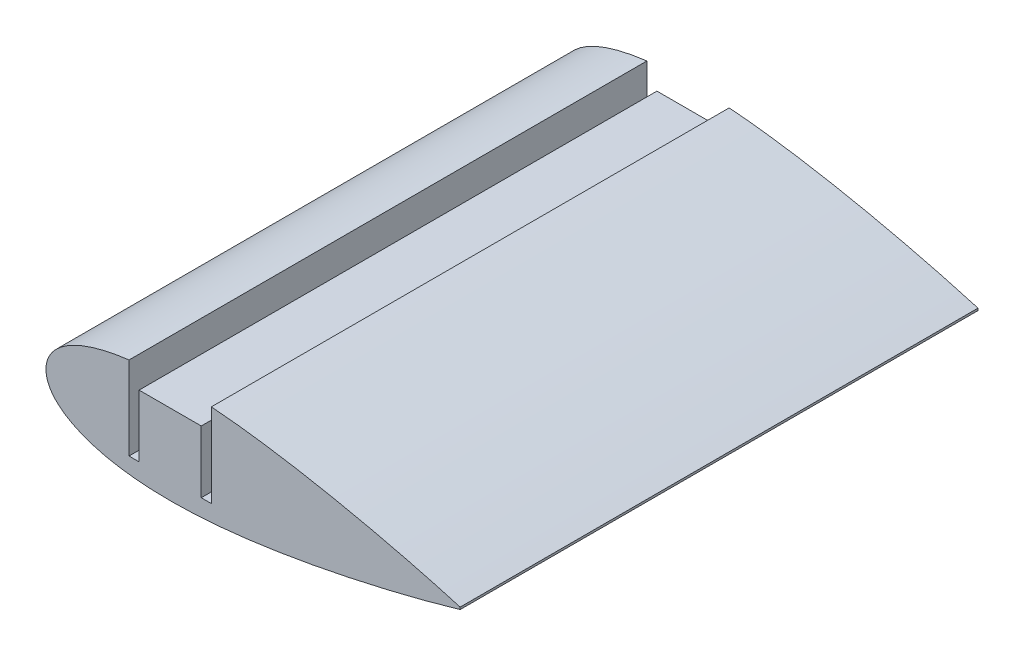
SolidWorks part; units mm, degrees
ref_plane "Спереди" through (0, 0, 0) normal (0, 0, 1) x (1, 0, 0)
ref_plane "Сверху" through (0, 0, 0) normal (0, 1, 0) x (1, 0, 0)
ref_plane "Справа" through (0, 0, 0) normal (1, 0, 0) x (0, 0, -1)
other "Configuration Table"
curve "Curve1"
  spline degree 3 poles (1, 0.0026, 0) (0.9995, 0.0028, 0) (0.9974, 0.0034, 0) (0.9928, 0.0047, 0) (0.9852, 0.0069, 0) (0.9746, 0.01, 0) (0.961, 0.0138, 0) (0.9446, 0.0183, 0) (0.9255, 0.0235, 0) (0.9037, 0.0292, 0) (0.8794, 0.0355, 0) (0.8529, 0.0421, 0) (0.8241, 0.0491, 0) (0.7933, 0.0562, 0) (0.7607, 0.0635, 0) (0.7266, 0.0709, 0) (0.691, 0.0782, 0) (0.6542, 0.0854, 0) (0.6165, 0.0923, 0) (0.5781, 0.0988, 0) (0.5392, 0.1049, 0) (0.5, 0.1104, 0) (0.4609, 0.1152, 0) (0.422, 0.1192, 0) (0.3836, 0.1222, 0) (0.3458, 0.1243, 0) (0.3091, 0.1252, 0) (0.2735, 0.1249, 0) (0.2392, 0.1234, 0) (0.2066, 0.1205, 0) (0.1758, 0.1164, 0) (0.147, 0.111, 0) (0.1203, 0.1043, 0) (0.096, 0.0965, 0) (0.0741, 0.0875, 0) (0.0549, 0.0774, 0) (0.0383, 0.0665, 0) (0.0245, 0.0546, 0) (0.0137, 0.042, 0) (0.0058, 0.0286, 0) (0.001, 0.0145, 0) (-0.0005, 0, 0) (0.001, -0.0145, 0) (0.0058, -0.0286, 0) (0.0137, -0.042, 0) (0.0245, -0.0546, 0) (0.0383, -0.0665, 0) (0.0549, -0.0774, 0) (0.0741, -0.0875, 0) (0.096, -0.0965, 0) (0.1203, -0.1043, 0) (0.147, -0.111, 0) (0.1758, -0.1164, 0) (0.2066, -0.1205, 0) (0.2392, -0.1234, 0) (0.2735, -0.1249, 0) (0.3091, -0.1252, 0) (0.3458, -0.1243, 0) (0.3836, -0.1222, 0) (0.422, -0.1192, 0) (0.4609, -0.1152, 0) (0.5, -0.1104, 0) (0.5392, -0.1049, 0) (0.5781, -0.0988, 0) (0.6165, -0.0923, 0) (0.6542, -0.0854, 0) (0.691, -0.0782, 0) (0.7266, -0.0709, 0) (0.7607, -0.0635, 0) (0.7933, -0.0562, 0) (0.8241, -0.0491, 0) (0.8529, -0.0421, 0) (0.8794, -0.0355, 0) (0.9037, -0.0292, 0) (0.9255, -0.0235, 0) (0.9446, -0.0183, 0) (0.961, -0.0138, 0) (0.9746, -0.01, 0) (0.9852, -0.0069, 0) (0.9928, -0.0047, 0) (0.9974, -0.0034, 0) (0.9995, -0.0028, 0) (1, -0.0026, 0) knots 0 0 0 0 0.000754 0.003013 0.006759 0.011967 0.018601 0.026614 0.035953 0.046555 0.058348 0.071256 0.085193 0.100071 0.115793 0.132259 0.149363 0.166997 0.185048 0.203403 0.221946 0.240561 0.259134 0.27755 0.295701 0.313483 0.330797 0.347552 0.363666 0.379065 0.393686 0.407475 0.420392 0.432406 0.443503 0.453686 0.462984 0.471456 0.479204 0.486388 0.493229 0.5 0.506771 0.513612 0.520796 0.528544 0.537016 0.546314 0.556497 0.567594 0.579608 0.592525 0.606314 0.620935 0.636334 0.652448 0.669203 0.686517 0.704299 0.72245 0.740866 0.759439 0.778054 0.796597 0.814952 0.833003 0.850637 0.867741 0.884207 0.899929 0.914807 0.928744 0.941652 0.953445 0.964047 0.973386 0.981399 0.988033 0.993241 0.996987 0.999246 1 1 1 1
sketch "Sketch2" plane through (0, 0, 0) normal (0, 0, 1) x (1, 0, 0)
  line L0 (55.999, 0.2099) -> (55.999, -0.2099) construction
  line L1 (55.999, 0) -> (-23.9777, 0) construction
  line L2 (-23.9777, 0) -> (-23.9777, 20.1567) construction
  line L3 (-7.5754, 10) -> (21.8908, 10) construction
  line L4 (55.999, 0.2099) -> (55.999, -0.2099)
  line L5 (0, 10) -> (0, -10) construction
  line L6 (55.999, -0.2099) -> (55.999, 14.9208) construction
  spline S1 degree 3 poles (55.999, 0.2099) (53.4639, 0.9505) (48.8039, 2.2339) (42.4289, 3.8199) (36.7434, 5.1209) (31.1997, 6.2872) (25.2824, 7.4075) (20.1765, 8.2452) (14.9796, 8.9749) (10.8215, 9.4486) (6.6974, 9.777) (3.6807, 9.9396) (0.7396, 10.0127) (-2.1078, 9.99) (-4.8439, 9.867) (-7.4522, 9.6409) (-9.9165, 9.3106) (-12.2218, 8.8772) (-14.354, 8.3437) (-16.3004, 7.7143) (-18.0494, 6.9954) (-19.5906, 6.1934) (-20.9154, 5.3156) (-22.0159, 4.3681) (-22.8849, 3.3565) (-23.5145, 2.285) (-23.8954, 1.1588) (-24.0187, 0) (-23.8954, -1.1588) (-23.5145, -2.285) (-22.8849, -3.3565) (-22.0159, -4.3681) (-20.9154, -5.3156) (-19.5906, -6.1934) (-18.0494, -6.9954) (-16.3004, -7.7143) (-14.354, -8.3437) (-12.2218, -8.8772) (-9.9165, -9.3106) (-7.4522, -9.6409) (-4.8439, -9.867) (-2.1078, -9.99) (0.7396, -10.0127) (3.6807, -9.9396) (7.7407, -9.7208) (12.9128, -9.2413) (19.1367, -8.4158) (25.2824, -7.4074) (31.1998, -6.2873) (37.5172, -4.9581) (44.7426, -3.2759) (51.0576, -1.6263) (54.945, -0.5178) (55.9579, -0.2219) (55.999, -0.2099) knots 0 0 0 0 0.046555 0.085193 0.115793 0.149363 0.185048 0.221946 0.240561 0.27755 0.295701 0.313483 0.330797 0.347552 0.363666 0.379065 0.393686 0.407475 0.420392 0.432406 0.443503 0.453686 0.462984 0.471456 0.479204 0.486388 0.493229 0.5 0.506771 0.513612 0.520796 0.528544 0.537016 0.546314 0.556497 0.567594 0.579608 0.592525 0.606314 0.620935 0.636334 0.652448 0.669203 0.686517 0.704299 0.740866 0.778054 0.814952 0.850637 0.884207 0.928744 0.981399 0.999246 1 1 1 1
  point P11 (0, 0)
  dimension "D1" = 20
extrude "Boss-Extrude1" add sketch "Sketch2" along normal blind 100
sketch "Sketch3" plane through (0, 0, 0) normal (0, 0, -1) x (-1, 0, 0)
  line L0 (6, -6.5) -> (7.95, -6.5)
  line L2 (-6, -6.5) -> (-6, 5.5)
  line L3 (-6, 5.5) -> (6, 5.5)
  line L4 (6, -6.5) -> (6, 5.5)
  line L5 (-6, -6.5) -> (6, 5.5) construction
  line L6 (-6, 5.5) -> (6, -6.5) construction
  line L7 (7.95, -6.5) -> (7.95, 9.5637)
  line L8 (-6, -6.5) -> (-7.95, -6.5)
  line L9 (-7.95, -6.5) -> (-7.95, 9.6738)
  line L10 (-11.2468, 10) -> (11.5184, 10) construction
  line L11 (0, 0) -> (0, 6.0357) construction
  line L12 (-7.95, -6.5) -> (7.95, -6.5) construction
  spline S0 degree 3 poles (275.2851, -1947.3186) (-351.5026, -245.2226) (-218.8463, -40.0718) (-42.4289, 3.8199) (-36.7434, 5.1209) (-31.1997, 6.2872) (-25.2824, 7.4075) (-20.1765, 8.2452) (-14.9796, 8.9749) (-10.8215, 9.4486) (-6.6974, 9.777) (-3.6807, 9.9396) (-0.7396, 10.0127) (2.1078, 9.99) (4.8439, 9.867) (7.4522, 9.6409) (9.9165, 9.3106) (12.2218, 8.8772) (14.354, 8.3437) (16.3004, 7.7143) (18.0494, 6.9954) (19.5906, 6.1934) (20.9154, 5.3156) (22.0159, 4.3681) (22.8849, 3.3565) (23.5145, 2.285) (23.8954, 1.1588) (24.0187, 0) (23.8954, -1.1588) (23.5145, -2.285) (22.8849, -3.3565) (22.0159, -4.3681) (20.9154, -5.3156) (19.5906, -6.1934) (18.0494, -6.9954) (16.3004, -7.7143) (14.354, -8.3437) (12.2218, -8.8772) (9.9165, -9.3106) (7.4522, -9.6409) (4.8439, -9.867) (2.1078, -9.99) (-0.7396, -10.0127) (-3.6807, -9.9396) (-7.7407, -9.7208) (-12.9128, -9.2413) (-19.1367, -8.4158) (-25.2824, -7.4074) (-31.1998, -6.2873) (-37.5172, -4.9581) (-44.7426, -3.2759) (-51.0576, -1.6263) (-78.1348, 6.0944) (-101.2564, 16.704) (-685.5525, -1897.6172) knots -3.088599 -3.088599 -3.088599 -3.088599 0.046555 0.085193 0.115793 0.149363 0.185048 0.221946 0.240561 0.27755 0.295701 0.313483 0.330797 0.347552 0.363666 0.379065 0.393686 0.407475 0.420392 0.432406 0.443503 0.453686 0.462984 0.471456 0.479204 0.486388 0.493229 0.5 0.506771 0.513612 0.520796 0.528544 0.537016 0.546314 0.556497 0.567594 0.579608 0.592525 0.606314 0.620935 0.636334 0.652448 0.669203 0.686517 0.704299 0.740866 0.778054 0.814952 0.850637 0.884207 0.928744 0.981399 0.999246 1.425061 1.425061 1.425061 1.425061 only from (-55.999, 0.2099) to (-55.999, -0.2099) construction
  spline S1 degree 3 poles (-7.95, 9.6738) (-7.5253, 9.7065) (-6.0943, 9.8095) (-3.6807, 9.9396) (-0.7396, 10.0127) (2.1078, 9.99) (4.8439, 9.867) (6.7781, 9.6993) (7.7981, 9.5819) (7.95, 9.5637) knots 0.288193 0.288193 0.288193 0.288193 0.295701 0.313483 0.330797 0.347552 0.363666 0.379065 0.381762 0.381762 0.381762 0.381762
  point P0 (0, -0.5)
  point P13 (-6.975, -6.5)
  dimension "D1" = 12
  dimension "D2" = 12
  dimension "D3" = 1.95
  dimension "D4" = 1.95
  dimension "D5" = 16.5
extrude "Cut-Extrude1" cut sketch "Sketch3" against normal up to next
